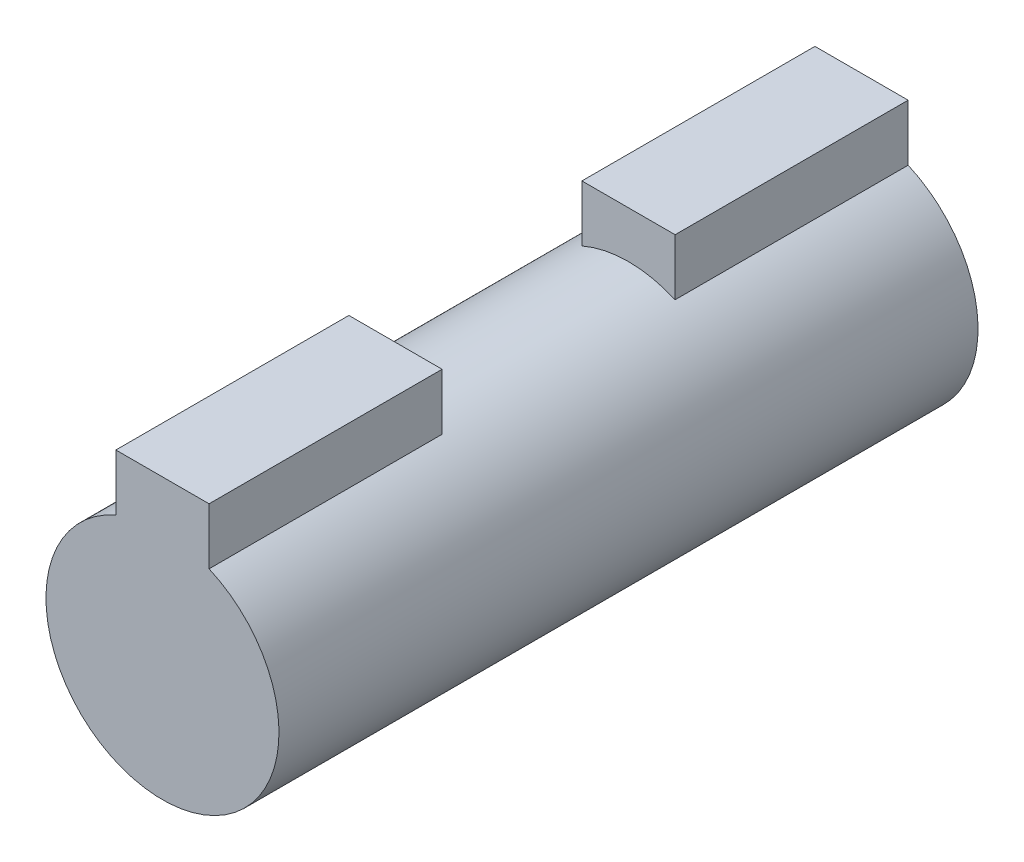
SolidWorks part; units mm, degrees
ref_plane "Front Plane" through (0, 0, 0) normal (0, 0, 1) x (1, 0, 0)
ref_plane "Top Plane" through (0, 0, 0) normal (0, 1, 0) x (1, 0, 0)
ref_plane "Right Plane" through (0, 0, 0) normal (1, 0, 0) x (0, 0, -1)
sketch "Sketch1" plane through (0, 0, 0) normal (0, 0, 1) x (1, 0, 0)
  line L1 (-2, 7) -> (2, 7)
  line L2 (-2, 7) -> (-2, 3)
  line L3 (-2, 3) -> (2, 3)
  line L4 (2, 7) -> (2, 3)
  line L5 (0, 3) -> (0, 7) construction
  line L6 (-2, 5) -> (2, 5) construction
  circle A0 centre (0, 0) radius 5
  point P3 (0, 5)
  dimension "D1" = 10
  dimension "D2" = 4
  dimension "D3" = 7
extrude "Boss-Extrude1" add sketch "Sketch1" along normal blind 30 contours L2 A0 L4 L3 | A0 L4 L1 L2 | L4 A0 L2 L3 region at (0, 5.9281, 0) region at (0, 3.9357, 0) region at (0, -0.4126, 0)
sketch "Sketch2" plane through (0, 0, 30) normal (0, 0, 1) x (1, 0, 0)
  circle A0 centre (0, 0) radius 5
  circle A1 centre (0, 0) radius 10
  dimension "D1" = 20
extrude "Cut-Extrude1" cut sketch "Sketch2" against normal blind 10 from offset 10 offset against normal yes
